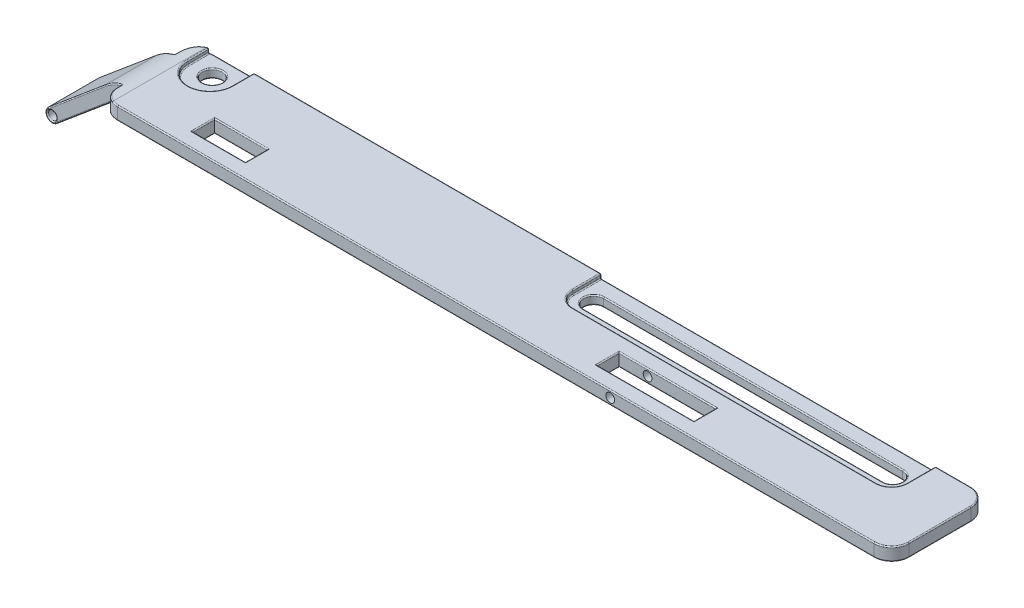
SolidWorks part; units mm, degrees
ref_plane "Front Plane" through (0, 0, 0) normal (0, 0, 1) x (1, 0, 0)
ref_plane "Top Plane" through (0, 0, 0) normal (0, 1, 0) x (1, 0, 0)
ref_plane "Right Plane" through (0, 0, 0) normal (1, 0, 0) x (0, 0, -1)
sketch "Sketch1" plane through (0, 0, 0) normal (0, 0, 1) x (1, 0, 0)
  line L0 (-182.7882, -2.3396) -> (-195, -12.5865)
  line L1 (0, 0) -> (-176.3603, 0)
  line L2 (0, 0) -> (0, 3)
  line L3 (0, 3) -> (-177.4522, 3)
  line L6 (-196.9284, -10.2884) -> (-183.8801, 0.6604)
  arc A0 (-196.9284, -10.2884) -> (-195, -12.5865) centre (-195.9642, -11.4374) ccw
  circle A1 centre (-195.9642, -11.4374) radius 1
  arc A2 (-176.3603, 0) -> (-182.7882, -2.3396) centre (-176.3603, -10) ccw
  arc A3 (-177.4522, 3) -> (-183.8801, 0.6604) centre (-177.4522, -7) ccw
  point P11 (-180, 0)
  dimension "D1" = 2
  dimension "D2" = 10
  dimension "D6" = 10
  dimension "D3" = 140
  dimension "D4" = 15
  dimension "D5" = 3
extrude "Boss-Extrude1" add sketch "Sketch1" along normal blind 11 and the other way blind 11
sketch "Sketch2" plane through (0, 0, 11) normal (0, 0, 1) x (1, 0, 0)
  line L0 (0, 0) -> (0, 3) construction
  line L1 (-210.1499, 9.6657) -> (-180, 9.6657)
  line L2 (-210.1499, 9.6657) -> (-210.1499, -17.5852)
  line L3 (-210.1499, -17.5852) -> (-180, -17.5852)
  line L4 (-180, 9.6657) -> (-180, -17.5852)
  dimension "D1" = 180
extrude "Cut-Extrude1" cut sketch "Sketch2" against normal blind 5
sketch "Sketch3" plane through (0, 0, -11) normal (0, 0, -1) x (-1, 0, 0)
  line L0 (0, 0) -> (0, 3) construction
  line L1 (180, 28.7292) -> (251.8205, 28.7292)
  line L2 (180, 28.7292) -> (180, -54.8714)
  line L3 (180, -54.8714) -> (251.8205, -54.8714)
  line L4 (251.8205, 28.7292) -> (251.8205, -54.8714)
  dimension "D1" = 180
extrude "Cut-Extrude2" cut sketch "Sketch3" against normal blind 5
sketch "Sketch4" plane through (0, 3, 0) normal (0, 1, 0) x (1, 0, 0)
  line L0 (0, -11) -> (-177.4522, -11) construction
  line L1 (-162.4522, -2.5) -> (-150.4522, -2.5)
  line L2 (-162.4522, -2.5) -> (-162.4522, -7.5)
  line L3 (-162.4522, -7.5) -> (-150.4522, -7.5)
  line L4 (-150.4522, -2.5) -> (-150.4522, -7.5)
  line L5 (-70.4522, -2.5) -> (-48.4522, -2.5)
  line L6 (-70.4522, -2.5) -> (-70.4522, -7.5)
  line L7 (-70.4522, -7.5) -> (-48.4522, -7.5)
  line L8 (-48.4522, -2.5) -> (-48.4522, -7.5)
  line L9 (-177.4522, 11) -> (-177.4522, -11) construction
  dimension "D1" = 5
  dimension "D2" = 12
  dimension "D3" = 3.5
  dimension "D4" = 15
  dimension "D5" = 3.5
  dimension "D6" = 80
  dimension "D7" = 22
  dimension "D8" = 5
extrude "Cut-Extrude3" cut sketch "Sketch4" against normal up to next
sketch "Sketch5" plane through (0, 3, 0) normal (0, 1, 0) x (1, 0, 0)
  line L0 (0, 11) -> (-177.4522, 11) construction
  line L1 (-88, 11) -> (-12, 11)
  line L2 (-88, 11) -> (-88, 4.5)
  line L3 (-84.5, 1) -> (-15.5, 1)
  line L4 (-12, 11) -> (-12, 4.5)
  line L5 (0, 11) -> (0, -11) construction
  line L10 (-180, 6) -> (-180, 11) construction
  line L11 (-177, 6) -> (-177, 11)
  line L12 (-177, 11) -> (-167, 11)
  line L13 (-167, 11) -> (-167, 6)
  arc A0 (-15.5, 1) -> (-12, 4.5) centre (-15.5, 4.5) ccw
  arc A1 (-84.5, 1) -> (-88, 4.5) centre (-84.5, 4.5) cw
  arc A2 (-177, 6) -> (-167, 6) centre (-172, 6) ccw
  point P14 (-12, 1)
  point P17 (-88, 1)
  dimension "D4" = 3.5
  dimension "D5" = 10
  dimension "D1" = 76
  dimension "D2" = 12
  dimension "D3" = 10
  dimension "D6" = 5
  dimension "D7" = 8
extrude "Cut-Extrude4" cut sketch "Sketch5" against normal blind 1
sketch "Sketch6" plane through (0, 3, 0) normal (0, 1, 0) x (1, 0, 0)
  line L1 (-84, 7.5) -> (-16, 7.5)
  line L3 (-84, 3) -> (-16, 3)
  line L6 (-12, 11) -> (-88, 11) construction
  line L7 (-12, 4.5) -> (-12, 11) construction
  line L8 (-177, 11) -> (-177, 6) construction
  arc A0 (-84, 7.5) -> (-84, 3) centre (-84, 5.25) ccw
  arc A1 (-16, 3) -> (-16, 7.5) centre (-16, 5.25) ccw
  circle A2 centre (-172, 6.5) radius 2.25
  arc A3 (-177, 6) -> (-167, 6) centre (-172, 6) ccw construction
  point P15 (-172, 1)
  dimension "D5" = 4.5
  dimension "D1" = 4.5
  dimension "D2" = 68
  dimension "D3" = 4
  dimension "D4" = 3.5
  dimension "D6" = 5.5
  dimension "D7" = 5
extrude "Cut-Extrude5" cut sketch "Sketch6" against normal up to next
fillet "Fillet1" radius 4 4 edges at (-180, 0.992, 11) (-180, 0.992, -11) (0, 1.5, 11) (0, 1.5, -11)
fillet "Fillet2" radius 0.25 86 edges at (-167, 2.5, -11) (-177, 2.5, -10.873) (-12, 2.5, -11) (-88, 2.5, -11) (-180, -0.6859, 6.5) (-178.6841, -0.2738, 9.9657) (-180, -0.6859, -6.5) (-179.1965, -0.4106, -9.4047) (-180, 2.67, -6.5) (-179.4342, 2.8016, -9.0509) (-180, 2.67, 6.5) (-179.1546, 2.854, 9.4593) (-167, 2, -8.5) (-172, 2, -1) (-177, 2, -8.4365) (-176.504, 2, -10.9681) (-171.5, 2, -11) (-174.25, 2, -6.5) (-196.9642, -11.4374, -6) (-181.4615, -1.399, -6) (-180, 0.992, -6) (-182.0511, 1.8797, -6) (-190.4042, -4.814, -6) (-197.1132, -12.4016, -6) (-188.8941, -7.463, -6) (-194.9642, -11.4374, 6) (-181.4615, -1.399, 6) (-188.8941, -7.463, 6) (-197.1132, -12.4016, 6) (-190.4042, -4.814, 6) (-182.0511, 1.8797, 6) (-180, 0.992, 6) (-1.1716, 0, 9.8284) (0, 0, 0) (-1.1716, 0, -9.8284) (-90, 0, -11) (-176.1803, 0, -10.9959) (-176.1803, 0, 10.9959) (-90, 0, 11) (-59.4522, 0, 2.5) (-48.4522, 0, 5) (-59.4522, 0, 7.5) (-70.4522, 0, 5) (-156.4522, 0, 2.5) (-150.4522, 0, 5) (-156.4522, 0, 7.5) (-162.4522, 0, 5) (-172, 0, -8.75) (-50, 0, -7.5) (-13.75, 0, -5.25) (-50, 0, -3) (-86.25, 0, -5.25) (-50, 2, -11) (-12, 2, -7.75) (-13.0251, 2, -2.0251) (-50, 2, -1) (-86.9749, 2, -2.0251) (-88, 2, -7.75) (-13.75, 2, -5.25) (-50, 2, -7.5) (-86.25, 2, -5.25) (-50, 2, -3) (-59.4522, 3, 7.5) (-48.4522, 3, 5) (-59.4522, 3, 2.5) (-70.4522, 3, 5) (-156.4522, 3, 7.5) (-150.4522, 3, 5) (-156.4522, 3, 2.5) (-162.4522, 3, 5) (-177.2283, 3, -10.8068) (-177, 3, -8.4365) (-172, 3, -1) (-167, 3, -8.5) (-127.5, 3, -11) (-88, 3, -7.75) (-86.9749, 3, -2.0251) (-50, 3, -1) (-13.0251, 3, -2.0251) (-12, 3, -7.75) (-8, 3, -11) (-1.1716, 3, -9.8284) (0, 3, 0) (-1.1716, 3, 9.8284) (-90, 3, 11) (-176.7388, 3, 10.9312)
sketch "Sketch7" plane through (0, 0, 11) normal (0, 0, 1) x (1, 0, 0)
  line L0 (-4, 2.75) -> (-176, 2.75) construction
  line L1 (-4, 0.25) -> (-4, 2.75) construction
  point P0 (-64, 1.5)
  dimension "D1" = 1.25
  dimension "D2" = 60
hole_wizard "1/16 (0.07874016) Diameter Hole1" positions "Sketch9" profile "Sketch10" hole size "1/16" standard "ANSI Inch"
sketch "Sketch9" plane through (0, 0, 11) normal (0, 0, 1) x (1, 0, 0)
  point P0 (-64, 1.5)
sketch "Sketch10" plane through (-64, 1.5, 11) normal (1, 0, 0) x (0, -1, 0)
  line L0 (0, 0) -> (0, 12)
  line L1 (0, 12) -> (1, 11.3991)
  line L2 (1, 11.3991) -> (1, 0)
  line L5 (1, 0) -> (0, 0)
  line L10 (0, 12) -> (-1, 11.3991) construction
  line L11 (0, -6.35) -> (0, 107.95) construction
  dimension "Hole Dia." = 2
  dimension "Hole Depth" = 12
  dimension "Drill Angle" = 118
